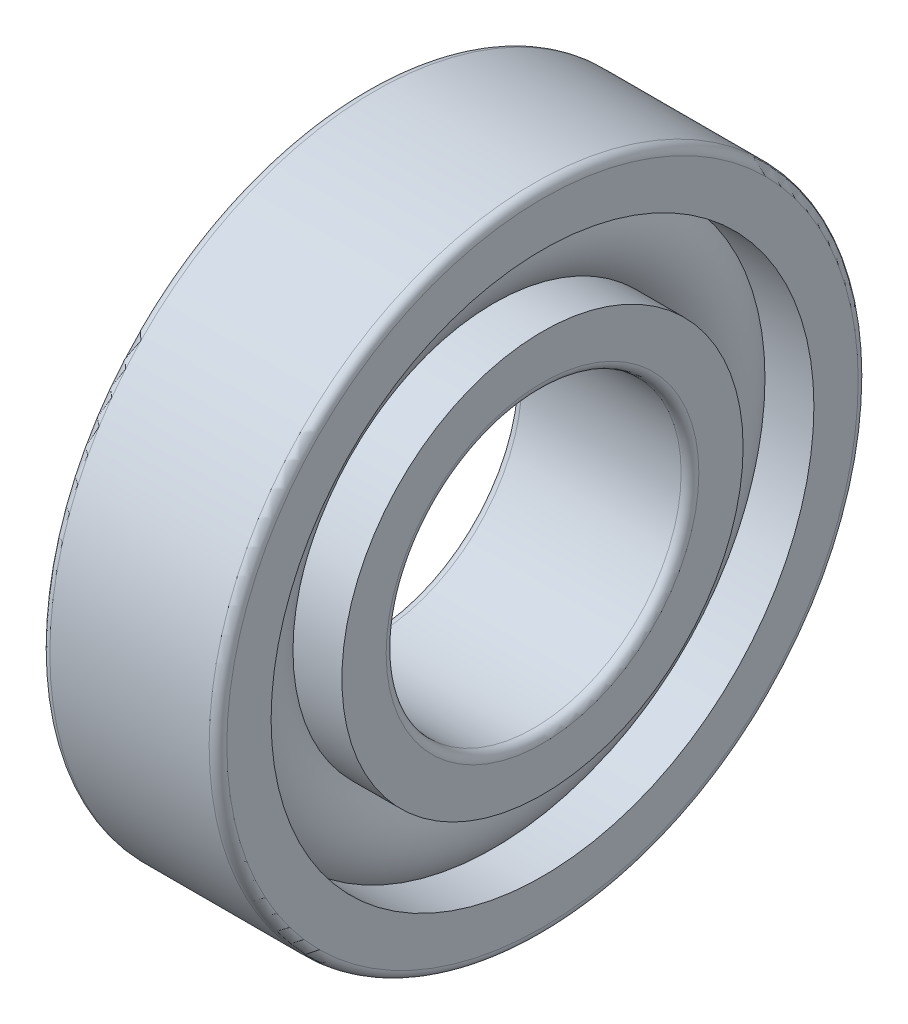
SolidWorks part; units mm, degrees
ref_plane "Plane1" through (0, 0, 0) normal (0, 0, 1) x (1, 0, 0)
ref_plane "Plane2" through (0, 0, 0) normal (0, 1, 0) x (1, 0, 0)
ref_plane "Plane3" through (0, 0, 0) normal (1, 0, 0) x (0, 0, -1)
sketch "Clipboard" plane through (0, 0, 0) normal (0, 0, 1) x (1, 0, 0)
  line L0 (-10, 0) -> (10, 0) construction
  line L1 (0, 0) -> (22.3471, -0.7804)
  line L2 (0, 0) -> (3.9976, 0.1396)
  line L3 (0, 0) -> (22.3471, -0.7804)
  line L4 (0, 0) -> (-22.3573, -0.3902)
  dimension "BallCLRad" = 4
  dimension "Count" = 2
  dimension "Show_count" = 2
  dimension "Max_count" = 2
  dimension "Min_count" = 1
sketch "CagSpiSke" plane through (0, 0, 0) normal (0, 0, 1) x (1, 0, 0)
  line L0 (0.09, 3.85) -> (0.09, 4.15)
  line L1 (0.09, 4.15) -> (-0.09, 4.15)
  line L2 (-0.09, 4.15) -> (-0.09, 3.85)
  line L3 (-0.09, 3.85) -> (0.09, 3.85)
  line L4 (-20.6375, 0) -> (20.6375, 0) construction
  line L5 (0, 0) -> (0, 23.7692) construction
  dimension "Thickness" = 0.18
  dimension "OD" = 8.3
  dimension "ID" = 7.7
revolve "CageSpine" add sketch "CagSpiSke" angle 0.001 about L4 reverse direction yes
ref_axis "Axis1" through (-50, 0, 0) along (1, 0, 0)
sketch "CagBalSke" plane through (0, 0, 0) normal (0, 0, 1) x (1, 0, 0)
  line L0 (-0.99, 4) -> (0.99, 4)
  line L1 (-1.905, 4) -> (1.905, 4) construction
  line L2 (-10, 0) -> (10, 0) construction
  line L3 (0, 0) -> (0, 24) construction
  arc A0 (0.99, 4) -> (-0.99, 4) centre (0, 4) cw
  dimension "CageWallOD" = 1.98
  dimension "BallCLRad" = 4
revolve "CageBall" [suppressed] add sketch "CagBalSke" angle 360 about L1 reverse direction yes
pattern_circular "CageBalls" [suppressed] count 2 every 180 about axis through (-50, 0, 0) along (1, 0, 0)
sketch "CagTrmODSke" plane through (0, 0, 0) normal (0, 0, 1) x (1, 0, 0)
  line L0 (0.991, 4.15) -> (0.991, 4.991)
  line L1 (0.991, 4.991) -> (-0.991, 4.991)
  line L2 (-0.991, 4.991) -> (-0.991, 4.15)
  line L3 (-0.991, 4.15) -> (0.991, 4.15)
  line L4 (-20.6375, 0) -> (20.6375, 0) construction
  line L5 (0, 0) -> (0, 25) construction
  dimension "Width" = 1.982
  dimension "ID" = 8.3
  dimension "OD" = 9.982
revolve "CageTrimOD" [suppressed] cut sketch "CagTrmODSke" angle 360 about L4 reverse direction yes
sketch "CagTrmIDSke" plane through (0, 0, 0) normal (0, 0, 1) x (1, 0, 0)
  line L0 (0.991, 3.011) -> (0.991, 3.85)
  line L1 (0.991, 3.85) -> (-0.991, 3.85)
  line L2 (-0.991, 3.85) -> (-0.991, 3.011)
  line L3 (-0.991, 3.011) -> (0.991, 3.011)
  line L4 (-20.6375, 0) -> (20.6375, 0) construction
  line L5 (0, 0) -> (0, 25) construction
  dimension "ID" = 6.022
  dimension "OD" = 7.7
  dimension "Width" = 1.982
revolve "CageTrimID" [suppressed] cut sketch "CagTrmIDSke" angle 360 about L4 reverse direction yes
sketch "BalSimSke" plane through (0, 0, 0) normal (0, 0, 1) x (1, 0, 0)
  line L0 (-10, 0) -> (10, 0) construction
  line L1 (-10, 4) -> (10, 4) construction
  line L2 (0, 0) -> (0, 23) construction
  circle A0 centre (0, 4) radius 0.9
  dimension "Ball_diameter" = 1.8
  dimension "BallCLRad" = 4
revolve "BallsSimplified" add sketch "BalSimSke" angle 360 about L0
sketch "BalDetSke" plane through (0, 0, 0) normal (0, 0, 1) x (1, 0, 0)
  line L0 (-0.9, 4) -> (0.9, 4)
  line L1 (-1.905, 4) -> (1.905, 4) construction
  line L2 (0, 0) -> (0, 25) construction
  arc A0 (0.9, 4) -> (-0.9, 4) centre (0, 4) cw
  dimension "Ball_diameter" = 1.8
  dimension "BallCLRad" = 4
revolve "BallDetailed" [suppressed] add sketch "BalDetSke" angle 360 about L1 reverse direction yes
sketch "InnRacSke" plane through (0, 0, 0) normal (0, 0, 1) x (1, 0, 0)
  line L0 (-0.6369, 3.4) -> (-1.5, 3.4)
  line L1 (-1.5, 3.4) -> (-1.5, 2.65)
  line L2 (-1.35, 2.5) -> (1.35, 2.5)
  line L3 (1.5, 2.65) -> (1.5, 3.4)
  line L4 (1.5, 3.4) -> (0.6369, 3.4)
  line L5 (-20.6375, 0) -> (20.6375, 0) construction
  line L6 (0, 0) -> (0, 30) construction
  arc A0 (-1.5, 2.65) -> (-1.35, 2.5) centre (-1.35, 2.65) ccw
  arc A1 (1.35, 2.5) -> (1.5, 2.65) centre (1.35, 2.65) ccw
  arc A2 (0.6369, 3.4) -> (-0.6369, 3.4) centre (0, 4) cw
  dimension "Fillet_radius" = 0.15
  dimension "Ball_diameter" = 1.75
  dimension "ID" = 5
  dimension "OD" = 6.8
  dimension "Width" = 3
  dimension "BallCLRad" = 4
revolve "InnerRace" add sketch "InnRacSke" angle 360 about L5 reverse direction yes
sketch "OutRacSke" plane through (0, 0, 0) normal (0, 0, 1) x (1, 0, 0)
  line L0 (-0.6369, 4.6) -> (-1.5, 4.6)
  line L1 (-1.5, 4.6) -> (-1.5, 5.35)
  line L2 (-1.35, 5.5) -> (1.35, 5.5)
  line L3 (1.5, 5.35) -> (1.5, 4.6)
  line L4 (1.5, 4.6) -> (0.6369, 4.6)
  line L5 (-20.6375, 0) -> (20.6375, 0) construction
  line L6 (0, 0) -> (0, 30) construction
  arc A0 (-1.5, 5.35) -> (-1.35, 5.5) centre (-1.35, 5.35) cw
  arc A1 (1.35, 5.5) -> (1.5, 5.35) centre (1.35, 5.35) cw
  arc A2 (0.6369, 4.6) -> (-0.6369, 4.6) centre (0, 4) ccw
  dimension "Fillet_radius" = 0.15
  dimension "Ball_diameter" = 1.75
  dimension "OD" = 11
  dimension "ID" = 9.2
  dimension "Width" = 3
  dimension "BallCLRad" = 4
revolve "OuterRace" add sketch "OutRacSke" angle 360 about L5 reverse direction yes
pattern_circular "BallsDetailed" [suppressed] count 2 every 180 about axis through (-50, 0, 0) along (1, 0, 0)
equation "\"BallCLRad@Clipboard\" = ( \"OD@OutRacSke\" + \"ID@InnRacSke\" ) / 4"
equation "\"BallCLRad@BalSimSke\" = \"BallCLRad@Clipboard\""
equation "\"BallCLRad@BalDetSke\" = \"BallCLRad@Clipboard\""
equation "\"BallCLRad@InnRacSke\" = \"BallCLRad@Clipboard\""
equation "\"BallCLRad@OutRacSke\" = \"BallCLRad@Clipboard\""
equation "\"Ball_diameter@InnRacSke\" = \"Ball_diameter@BalDetSke\" - 0.05"
equation "\"Ball_diameter@OutRacSke\" = \"Ball_diameter@BalDetSke\" - 0.05"
equation "\"Ball_diameter@BalSimSke\" = \"Ball_diameter@BalDetSke\""
equation "\"Width@OutRacSke\" = \"Width@InnRacSke\""
equation "\"Fillet_radius@OutRacSke\" = \"Fillet_radius@InnRacSke\""
equation "\"Max_count@Clipboard\" = int( 3.14159265 / atn(( \"Ball_diameter@BalDetSke\" / 2) / sqr( \"BallCLRad@Clipboard\"  *  \"BallCLRad@Clipboard\" - ( \"Ball_diameter@BalDetSke\" / 2) *  ( \"Ball_diameter@BalDetSke\" / 2))))"
equation "\"Max_count@Clipboard\" = ((sgn( \"Max_count@Clipboard\" - \"Count@Clipboard\" )-1)*( \"Max_count@Clipboard\" - \"Count@Clipboard\" ))/-2+ \"Count@Clipboard\""
equation "\"Count@BallsDetailed\" = int( \"Show_count@Clipboard\" ) "
equation "\"Count@BallsDetailed\" = ((sgn( \"Count@BallsDetailed\" - \"Max_count@Clipboard\" )-1)*( \"Count@BallsDetailed\" - \"Max_count@Clipboard\" ))/-2+ \"Max_count@Clipboard\""
equation "\"Count@BallsDetailed\" = ((sgn( \"Count@BallsDetailed\" - \"Min_count@Clipboard\" )+1)*( \"Count@BallsDetailed\" - \"Min_count@Clipboard\"))/2 +\"Min_count@Clipboard\""
equation "\"Angle@BallsDetailed\" = 360.0 / \"Max_count@Clipboard\""
equation "\"BallCLRad@CagBalSke\" = \"BallCLRad@Clipboard\""
equation "\"Count@CageBalls\" = \"Count@BallsDetailed\""
equation "\"Angle@CageBalls\" = \"Angle@BallsDetailed\""
equation "\"Angle@CageSpine\" =  \"Angle@CageBalls\" * ( \"Count@CageBalls\" -1 + int( \"Count@CageBalls\" / \"Max_count@Clipboard\" ) )  + 0.001 -  int( \"Count@CageBalls\" / \"Max_count@Clipboard\" ) * 0.001"
equation "\"Angle@CageSpine\" =  \"Angle@CageSpine\" * int( \"Min_count@Clipboard\" / 2) + int(1 / \"Min_count@Clipboard\")  * 0.001"
equation "\"CageWallOD@CagBalSke\" =  \"Ball_diameter@BalDetSke\" * 1.1"
equation "\"Thickness@CagSpiSke\" =  \"Ball_diameter@BalDetSke\" * 0.1"
equation "\"OD@CagTrmODSke\" = \"BallCLRad@Clipboard\" * 2 + \"CageWallOD@CagBalSke\" + 0.002"
equation "\"ID@CagTrmODSke\" = \"BallCLRad@Clipboard\" * 2 + \"Ball_diameter@BalDetSke\" / 6"
equation "\"OD@CagTrmIDSke\" = \"BallCLRad@Clipboard\" * 2 - \"Ball_diameter@BalDetSke\" / 6"
equation "\"ID@CagTrmIDSke\" = \"BallCLRad@Clipboard\" * 2 - \"CageWallOD@CagBalSke\" + 0.002"
equation "\"OD@CagSpiSke\" = \"ID@CagTrmODSke\""
equation "\"ID@CagSpiSke\" = \"OD@CagTrmIDSke\""
equation "\"Width@CagTrmODSke\" = \"CageWallOD@CagBalSke\" + 0.002"
equation "\"Width@CagTrmIDSke\" = \"CageWallOD@CagBalSke\" + 0.002"
